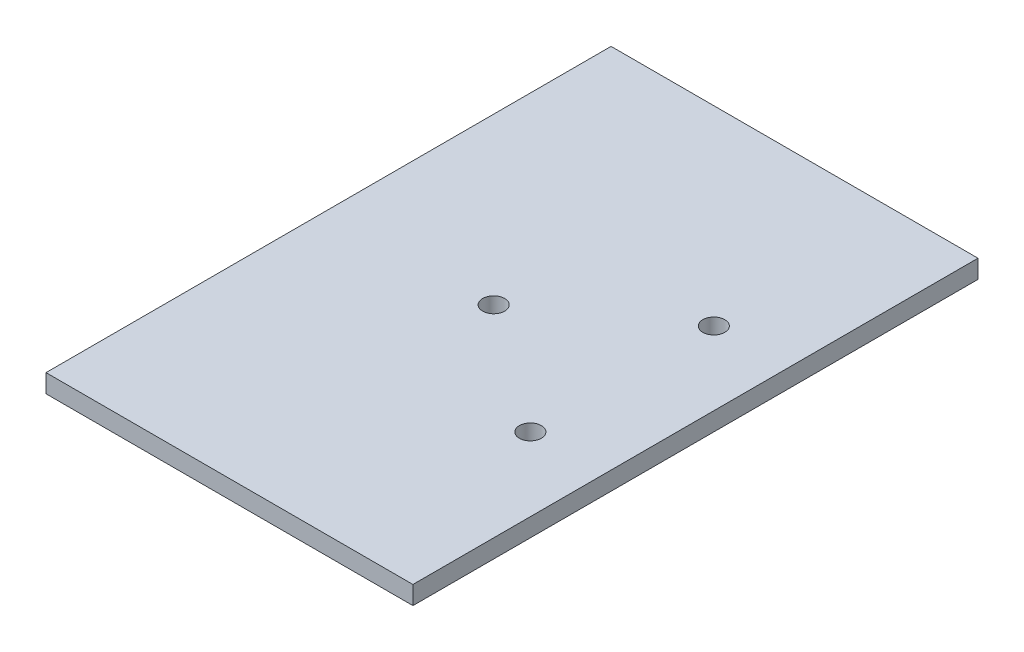
SolidWorks part; units mm, degrees
ref_plane "Front Plane" through (0, 0, 0) normal (0, 0, 1) x (1, 0, 0)
ref_plane "Top Plane" through (0, 0, 0) normal (0, 1, 0) x (1, 0, 0)
ref_plane "Right Plane" through (0, 0, 0) normal (1, 0, 0) x (0, 0, -1)
sketch "Sketch1" plane through (0, 0, 0) normal (0, 1, 0) x (1, 0, 0)
  line L0 (73.3491, 51.6462) -> (19.3491, 51.6462) construction
  line L1 (-26.6509, 128.6462) -> (73.3491, 128.6462)
  line L2 (-26.6509, 128.6462) -> (-26.6509, -25.3538)
  line L3 (-26.6509, -25.3538) -> (73.3491, -25.3538)
  line L4 (73.3491, 128.6462) -> (73.3491, -25.3538)
  line L5 (7.3491, 51.6462) -> (-26.6509, 51.6462) construction
  line L6 (73.3491, 51.6462) -> (-26.6509, 51.6462) construction
  circle A2 centre (18.3491, 51.6462) radius 3
  circle A3 centre (53.3491, 76.6462) radius 3
  circle A4 centre (53.3491, 26.6462) radius 3
  dimension "D3" = 6
  dimension "D4" = 6
  dimension "D1" = 154
  dimension "D2" = 100
  dimension "D5" = 55
  dimension "D6" = 20
  dimension "D7" = 25
extrude "Boss-Extrude1" add sketch "Sketch1" along normal blind 5
